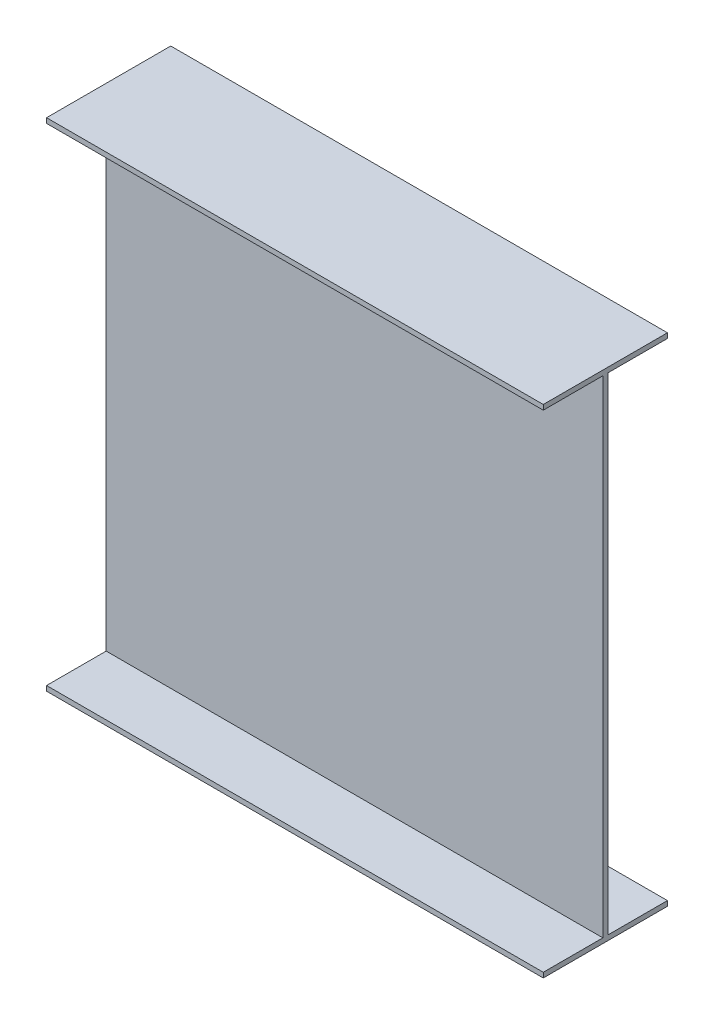
SolidWorks part; units mm, degrees
ref_plane "Front Plane" through (0, 0, 0) normal (0, 0, 1) x (1, 0, 0)
ref_plane "Top Plane" through (0, 0, 0) normal (0, 1, 0) x (1, 0, 0)
ref_plane "Right Plane" through (0, 0, 0) normal (1, 0, 0) x (0, 0, -1)
sketch "Sketch1" plane through (0, 0, 0) normal (1, 0, 0) x (0, 0, -1)
  line L0 (-4.5843, -956.1163) -> (115.4157, -956.1163)
  line L1 (-134.5843, 33.8837) -> (115.4157, 33.8837)
  line L2 (-134.5843, 33.8837) -> (-134.5843, 23.8837)
  line L3 (-134.5843, 23.8837) -> (-14.5843, 23.8837)
  line L4 (115.4157, 33.8837) -> (115.4157, 23.8837)
  line L5 (-134.5843, -956.1163) -> (-14.5843, -956.1163)
  line L6 (-134.5843, -956.1163) -> (-134.5843, -966.1163)
  line L7 (-134.5843, -966.1163) -> (115.4157, -966.1163)
  line L8 (115.4157, -956.1163) -> (115.4157, -966.1163)
  line L10 (-14.5843, 23.8837) -> (-14.5843, -956.1163)
  line L12 (-4.5843, 23.8837) -> (-4.5843, -956.1163)
  line L13 (-4.5843, 23.8837) -> (115.4157, 23.8837)
  line L14 (-14.5843, 23.8837) -> (-4.5843, 23.8837) construction
  dimension "D1" = 250
  dimension "D2" = 10
  dimension "D3" = 1000
extrude "Boss-Extrude1" add sketch "Sketch1" along normal blind 1000
